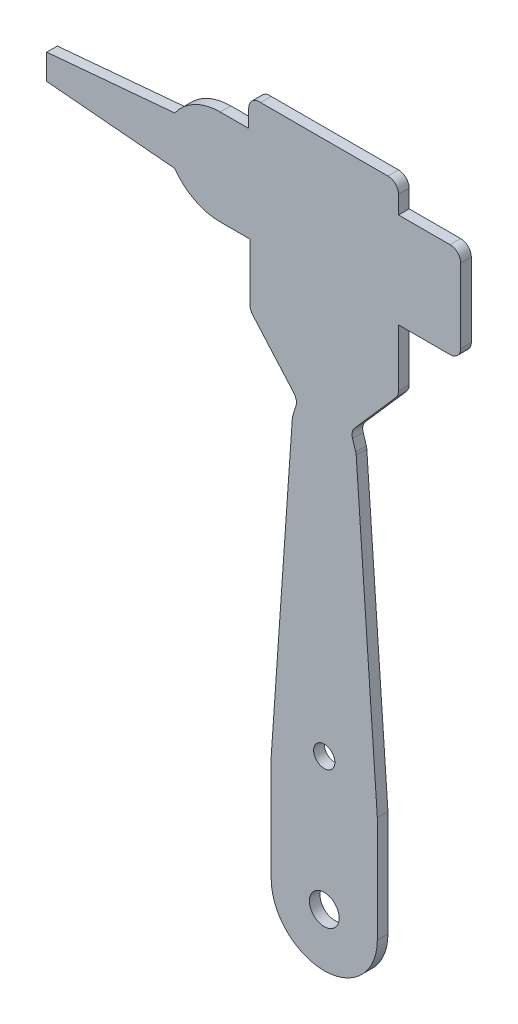
SolidWorks part; units mm, degrees
ref_plane "Alzado" through (0, 0, 0) normal (0, 0, 1) x (1, 0, 0)
ref_plane "Planta" through (0, 0, 0) normal (0, 1, 0) x (1, 0, 0)
ref_plane "Vista lateral" through (0, 0, 0) normal (1, 0, 0) x (0, 0, -1)
sketch "Model" plane through (0, 0, 0) normal (0, 0, 1) x (1, 0, 0)
  line L0 (57.0611, 44.4099) -> (52.206, 44.4099)
  line L1 (52.206, 44.4099) -> (52.206, 46.0853)
  line L2 (51.206, 47.0853) -> (39.206, 47.0853)
  line L3 (38.0907, 46.0853) -> (38.0907, 44.4099)
  line L4 (38.0907, 44.4099) -> (35.3933, 44.4099)
  line L5 (31.1229, 42.1874) -> (19.054, 41.1205)
  line L6 (19.054, 41.1205) -> (19.054, 38.7294)
  line L7 (19.054, 38.7294) -> (31.1229, 37.6625)
  line L8 (35.3933, 35.44) -> (38.206, 35.44)
  line L9 (38.206, 35.44) -> (38.206, 30.0497)
  line L10 (38.4539, 29.3907) -> (42.3364, 24.9601)
  line L11 (42.5389, 24.0031) -> (42.2409, 23.0482)
  line L12 (42.1979, 22.8197) -> (40.206, -5.7616)
  line L13 (40.206, -5.7616) -> (40.206, -15.7616)
  line L14 (50.206, -15.7616) -> (50.206, -5.7616)
  line L15 (50.206, -5.7616) -> (48.2141, 22.8197)
  line L16 (48.1711, 23.0482) -> (47.8731, 24.0031)
  line L17 (48.0756, 24.9601) -> (51.9581, 29.3907)
  line L18 (52.206, 30.0497) -> (52.206, 35.44)
  line L19 (52.206, 35.44) -> (57.0611, 35.44)
  line L20 (58.0611, 36.44) -> (58.0611, 43.4099)
  circle A0 centre (45.206, -3.2616) radius 1
  circle A1 centre (45.206, -15.7616) radius 1.4
  arc A2 (52.206, 46.0853) -> (51.206, 47.0853) centre (51.206, 46.0853) ccw
  arc A3 (39.206, 47.0853) -> (38.0907, 46.0853) centre (39.0907, 46.0919) ccw
  arc A4 (35.3933, 44.4099) -> (31.1229, 42.1874) centre (35.3933, 39.1959) ccw
  arc A5 (31.1229, 37.6625) -> (35.3933, 35.44) centre (35.3933, 40.654) ccw
  arc A6 (38.206, 30.0497) -> (38.4539, 29.3907) centre (39.206, 30.0497) ccw
  arc A7 (42.5389, 24.0031) -> (42.3364, 24.9601) centre (41.5843, 24.301) ccw
  arc A8 (42.2409, 23.0482) -> (42.1979, 22.8197) centre (43.1954, 22.7502) ccw
  arc A9 (40.206, -15.7616) -> (50.206, -15.7616) centre (45.206, -15.7616) ccw
  arc A10 (48.2141, 22.8197) -> (48.1711, 23.0482) centre (47.2165, 22.7502) ccw
  arc A11 (48.0756, 24.9601) -> (47.8731, 24.0031) centre (48.8276, 24.301) ccw
  arc A12 (51.9581, 29.3907) -> (52.206, 30.0497) centre (51.206, 30.0497) ccw
  arc A14 (58.0611, 43.4099) -> (57.0611, 44.4099) centre (57.0611, 43.4099) ccw
  arc A15 (58.0611, 36.44) -> (57.0611, 35.44) centre (57.0611, 36.44) cw
  point P36 (58.0611, 35.44)
  point P39 (58.0611, 44.4099)
  point P50 (0, 0)
  point P52 (0, 0)
  dimension "D1" = 1
  dimension "D2" = 1
base flange "Brida base1" sketch "Model" thickness 1 reverse thickness direction no parameters "D1"=0.7366
sketch "Líneas de pliegue1" [suppressed] plane through (0, 0, 0) normal (0, 1, 0) x (1, 0, 0)
sketch "Cuadro delimitador1" [suppressed] plane through (0, 0, 0) normal (0, 1, 0) x (1, 0, 0)
sheet metal parameters "Chapa metálica1" thickness 1 parameters "D1"=0.7366
flat pattern "Chapa desplegada1" [suppressed]
sketch "Líneas de pliegue2" plane through (0, 0, 0) normal (0, 1, 0) x (1, 0, 0)
sketch3d "Cuadro delimitador2" [suppressed]
  line L0 (-2.7179, 8.3457, 0) -> (-26.7784, -54.6866, 0) construction
  line L1 (32.9486, -5.2688, 0) -> (8.8881, -68.3011, 0) construction
  line L2 (-2.7179, 8.3457, 0) -> (32.9486, -5.2688, 0) construction
  line L3 (-26.7784, -54.6866, 0) -> (8.8881, -68.3011, 0) construction
